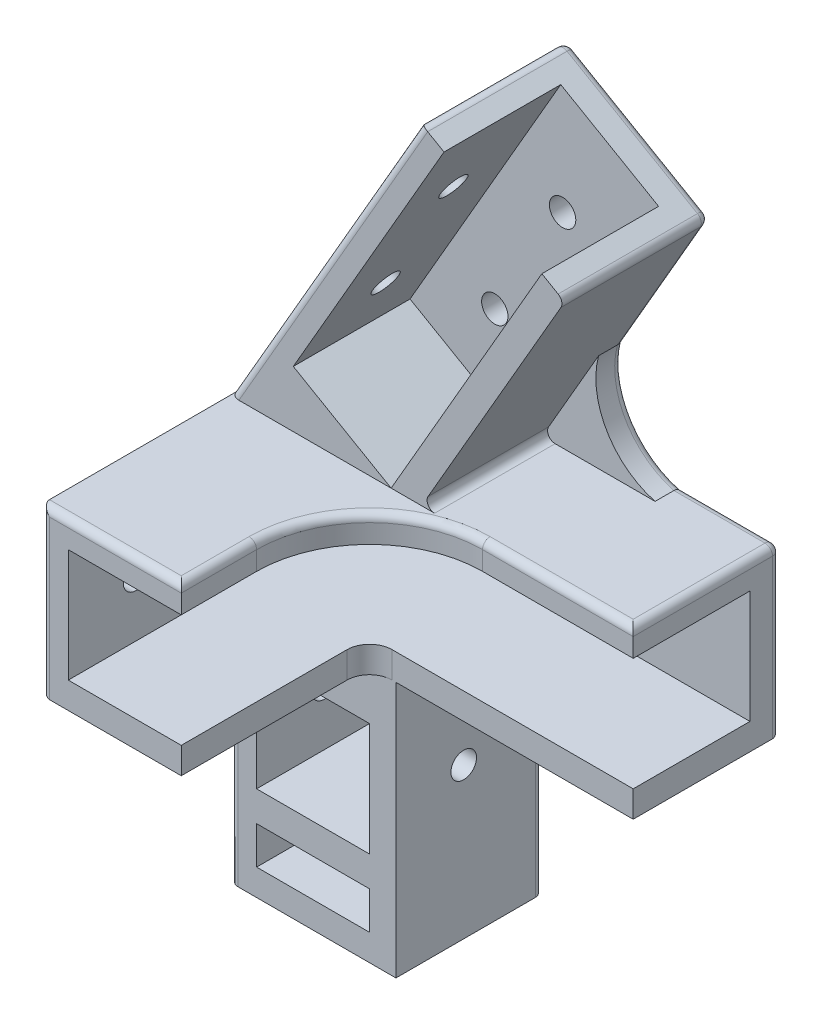
SolidWorks part; units mm, degrees
ref_plane "Front Plane" through (0, 0, 0) normal (0, 0, 1) x (1, 0, 0)
ref_plane "Top Plane" through (0, 0, 0) normal (0, 1, 0) x (1, 0, 0)
ref_plane "Right Plane" through (0, 0, 0) normal (1, 0, 0) x (0, 0, -1)
sketch "Sketch1" plane through (0, 0, 0) normal (0, 0, 1) x (1, 0, 0)
  line L1 (-5.6994, 32.9163) -> (16.3006, 32.9163)
  line L2 (-5.6994, 10.9163) -> (-5.6994, -23.0837)
  line L3 (-5.6994, -23.0837) -> (16.3006, -23.0837)
  line L4 (16.3006, 32.9163) -> (16.3006, -23.0837)
  line L5 (-5.6994, 10.9163) -> (-37.1994, 10.9163)
  line L7 (-5.6994, 32.9163) -> (-37.1994, 32.9163)
  line L8 (-37.1994, 10.9163) -> (-37.1994, 32.9163)
  dimension "D1" = 22
  dimension "D2" = 22
  dimension "D3" = 56
  dimension "D4" = 53.5
extrude "Boss-Extrude1" add sketch "Sketch1" along normal blind 19.5
sketch "Sketch3" plane through (0, 0, 19.5) normal (0, 0, 1) x (1, 0, 0)
  line L1 (16.3006, 32.9163) -> (-2.1994, 32.9163)
  line L2 (16.3006, 32.9163) -> (16.3006, 10.9163)
  line L3 (16.3006, 10.9163) -> (-2.1994, 10.9163)
  line L4 (-2.1994, 32.9163) -> (-2.1994, 10.9163)
  dimension "D1" = 18.5
extrude "Boss-Extrude2" add sketch "Sketch3" along normal blind 25
sketch "Sketch5" plane through (0, 0, 44.5) normal (0, 0, 1) x (1, 0, 0)
  line L0 (-37.1994, 32.9163) -> (-37.1994, 10.9163) construction
  line L1 (-37.1994, 29.4163) -> (12.8006, 29.4163)
  line L2 (-37.1994, 29.4163) -> (-37.1994, 14.4163)
  line L3 (-37.1994, 14.4163) -> (12.8006, 14.4163)
  line L4 (12.8006, 29.4163) -> (12.8006, 14.4163)
  line L5 (16.3006, 10.9163) -> (16.3006, 32.9163) construction
  line L6 (-2.1994, 4.4163) -> (12.8006, 4.4163)
  line L7 (-2.1994, 4.4163) -> (-2.1994, -10.5837)
  line L8 (-2.1994, -10.5837) -> (12.8006, -10.5837)
  line L9 (12.8006, 4.4163) -> (12.8006, -10.5837)
  line L12 (-2.1994, 32.9163) -> (-37.1994, 32.9163) construction
  line L13 (-2.1994, 10.9163) -> (16.3006, 10.9163) construction
  line L15 (16.3006, -23.0837) -> (16.3006, 10.9163) construction
  line L16 (-5.6994, -23.0837) -> (16.3006, -23.0837) construction
  line L17 (-2.1994, -14.5837) -> (12.8006, -14.5837)
  line L18 (-2.1994, -14.5837) -> (-2.1994, -19.5837)
  line L19 (-2.1994, -19.5837) -> (12.8006, -19.5837)
  line L20 (12.8006, -14.5837) -> (12.8006, -19.5837)
  dimension "D1" = 3.5
  dimension "D2" = 6.5
  dimension "D3" = 15
  dimension "D4" = 3.5
  dimension "D5" = 15
  dimension "D6" = 15
  dimension "D7" = 3.5
  dimension "D8" = 15
  dimension "D9" = 4
  dimension "D10" = 3.5
extrude "Cut-Extrude1" cut sketch "Sketch5" against normal offset from surface (40.5 mm away) 4 up to face at (-8.8661, 6.9163, 0)
sketch "Sketch7" plane through (16.3006, 0, 0) normal (1, 0, 0) x (0, 0, -1)
  line L0 (-34.5, 10.9163) -> (-19.5, 10.9163)
  line L1 (-44.5, 10.9163) -> (-19.5, 10.9163) construction
  line L2 (-19.5, 10.9163) -> (-19.5, -4.0837)
  line L3 (-19.5, -23.0837) -> (-19.5, 10.9163) construction
  arc A0 (-34.5, 10.9163) -> (-19.5, -4.0837) centre (-34.5, -4.0837) cw
  dimension "D1" = 15
extrude "Boss-Extrude4" add sketch "Sketch7" against normal blind 3.5
sketch "Sketch8" plane through (0, 0, 0) normal (0, 0, -1) x (-1, 0, 0)
  line L0 (5.6994, 10.9163) -> (20.6994, 10.9163)
  line L1 (37.1994, 10.9163) -> (5.6994, 10.9163) construction
  line L2 (5.6994, 10.9163) -> (5.6994, -4.0837)
  line L3 (5.6994, 10.9163) -> (5.6994, -23.0837) construction
  arc A0 (20.6994, 10.9163) -> (5.6994, -4.0837) centre (20.6994, -4.0837) ccw
  dimension "D1" = 15
extrude "Boss-Extrude5" add sketch "Sketch8" against normal blind 3.5
sketch "Sketch9" plane through (0, 32.9163, 0) normal (0, 1, 0) x (1, 0, 0)
  line L0 (-2.1994, -34.5) -> (-2.1994, -19.5)
  line L1 (-2.1994, -44.5) -> (-2.1994, -19.5) construction
  line L2 (-2.1994, -19.5) -> (-17.1994, -19.5)
  line L3 (-2.1994, -19.5) -> (-37.1994, -19.5) construction
  arc A0 (-2.1994, -34.5) -> (-17.1994, -19.5) centre (-17.1994, -34.5) ccw
  dimension "D1" = 15
extrude "Boss-Extrude6" add sketch "Sketch9" against normal blind 3.5
fillet "Fillet3" radius 3 1 edges
sketch "Sketch11" plane through (0, 0, 0) normal (0, 0, -1) x (-1, 0, 0)
  line L0 (1.1994, -23.0837) -> (1.1994, 10.9163) construction
  line L2 (5.6994, -23.0837) -> (-16.3006, -23.0837) construction
  line L5 (5.6994, -4.0837) -> (5.6994, -23.0837) construction
  text T0 "MR.3" font "Century Gothic" height 12
  dimension "D1" = 4.5
extrude "Cut-Extrude3" cut sketch "Sketch11" against normal blind 1
sketch "Sketch12" plane through (0, 0, 0) normal (0, 0, -1) x (-1, 0, 0)
  line L0 (37.1994, 21.9163) -> (-16.3006, 21.9163) construction
  line L1 (37.1994, 32.9163) -> (37.1994, 10.9163) construction
  line L2 (-16.3006, -23.0837) -> (-16.3006, 32.9163) construction
  line L3 (-12.8006, 14.4163) -> (-12.8006, 29.4163) construction
  circle A0 centre (-5.3006, 21.9163) radius 1.7
  circle A1 centre (10.9494, 21.9163) radius 1.7
  circle A2 centre (27.1994, 21.9163) radius 1.7
  dimension "D4" = 3.4
  dimension "D1" = 7.5
  dimension "D2" = 10
  dimension "D3" = 16.25
extrude "Cut-Extrude4" cut sketch "Sketch12" against normal blind 5
sketch "Sketch13" plane through (-5.6994, 0, 0) normal (-1, 0, 0) x (0, 0, 1)
  line L0 (4, 4.4163) -> (19.5, 4.4163) construction
  line L1 (19.5, 10.9163) -> (19.5, -23.0837) construction
  circle A0 centre (10.5, -3.0837) radius 1.7
  dimension "D2" = 9
  dimension "D3" = 3.4
  dimension "D1" = 7.5
extrude "Cut-Extrude5" cut sketch "Sketch13" against normal blind 45
sketch "Sketch14" plane through (16.3006, 0, 0) normal (1, 0, 0) x (0, 0, -1)
  line L0 (-10.5, -3.0837) -> (-10.5, 32.9163) construction
  line L1 (-44.5, 32.9163) -> (0, 32.9163) construction
  line L2 (-44.5, 21.9163) -> (-10.5, 21.9163) construction
  line L3 (-44.5, 10.9163) -> (-44.5, 32.9163) construction
  circle A0 centre (-10.5, 21.9163) radius 1.7
  circle A1 centre (-35.5, 21.9163) radius 1.7
  dimension "D1" = 3.4
  dimension "D2" = 9
extrude "Cut-Extrude6" cut sketch "Sketch14" against normal blind 45
sketch "Sketch15" plane through (0, -23.0837, 0) normal (0, -1, 0) x (1, 0, 0)
  line L0 (16.3006, 9.75) -> (-5.6994, 9.75) construction
  line L1 (16.3006, 19.5) -> (16.3006, 0) construction
  line L2 (-5.6994, 19.5) -> (-5.6994, 0) construction
  line L3 (5.3006, 19.5) -> (5.3006, 0) construction
  line L4 (-5.6994, 19.5) -> (16.3006, 19.5) construction
  line L5 (-5.6994, 0) -> (16.3006, 0) construction
  circle A0 centre (5.3006, 9.75) radius 1.7
  dimension "D1" = 3.4
extrude "Cut-Extrude7" cut sketch "Sketch15" against normal blind 4
mirror "Mirror2" about plane through (16.3006, 32.9163, 19.5) normal (-1, 0, 0) of "Cut-Extrude7", "Cut-Extrude6", "Cut-Extrude5", "Cut-Extrude4", "Fillet3", "Boss-Extrude6", "Boss-Extrude5", "Boss-Extrude4", "Cut-Extrude1", "Boss-Extrude2", "Boss-Extrude1"
sketch "Sketch16" plane through (0, 0, 0) normal (0, 0, -1) x (-1, 0, 0)
  line L0 (-69.8006, 32.9163) -> (37.1994, 32.9163) construction
  line L1 (-16.3006, 32.9163) -> (53.9943, 32.9163)
  line L2 (-16.3006, 32.9163) -> (-16.3006, -24.95)
  line L3 (-16.3006, -24.95) -> (53.9943, -24.95)
  line L4 (53.9943, 32.9163) -> (53.9943, -24.95)
extrude "Cut-Extrude8" cut sketch "Sketch16" against normal blind 72
sketch "Sketch20" plane through (0, 0, 0) normal (0, 0, -1) x (-1, 0, 0)
  line L0 (-22.3006, -23.0837) -> (-22.3006, 16.9163) construction
  line L1 (-16.3006, -23.0837) -> (-38.3006, -23.0837) construction
  line L2 (-16.3006, 32.9163) -> (-16.3006, -23.0837) construction
  text T0 "ALFR3D" font "Murder Of Mayday" height 10
  dimension "D1" = 6
  dimension "D2" = 40
extrude "Cut-Extrude9" [suppressed] cut sketch "Sketch20" against normal blind 1
sketch "Sketch21" plane through (0, 0, 0) normal (0, 0, -1) x (-1, 0, 0)
  line L0 (-16.3006, 32.9163) -> (-41.6514, 76.8252)
  line L1 (-41.6514, 76.8252) -> (-60.704, 65.8252)
  line L2 (-60.704, 65.8252) -> (-41.704, 32.9163)
  line L3 (-69.8006, 32.9163) -> (-16.3006, 32.9163) construction
  line L4 (-41.704, 32.9163) -> (-16.3006, 32.9163)
  dimension "D1" = 22
  dimension "D2" = 60
  dimension "D3" = 38
extrude "Boss-Extrude7" add sketch "Sketch21" against normal up to surface (19.5 mm away) up to face at (57.3006, 31.1663, 19.5)
sketch "Sketch22" plane through (0, 0, 19.5) normal (0, 0, 1) x (1, 0, 0)
  line L0 (44.6825, 75.0752) -> (24.6722, 40.4163)
  line L1 (60.704, 65.8252) -> (41.6514, 76.8252) construction
  line L2 (24.6722, 40.4163) -> (37.6625, 32.9163)
  line L3 (37.6625, 32.9163) -> (57.6729, 67.5752)
  line L4 (57.6729, 67.5752) -> (44.6825, 75.0752)
  line L5 (41.6514, 76.8252) -> (16.3006, 32.9163) construction
  line L7 (16.3006, 32.9163) -> (41.704, 32.9163) construction
  dimension "D1" = 15
  dimension "D2" = 3.5
extrude "Cut-Extrude10" cut sketch "Sketch22" against normal up to surface (15.5 mm away) up to face at (41.8506, 21.9163, 4)
sketch "Sketch23" plane through (0, 0, 0) normal (0, 0, -1) x (-1, 0, 0)
  line L0 (-56.704, 32.9163) -> (-41.704, 32.9163)
  line L1 (-69.8006, 32.9163) -> (-41.704, 32.9163) construction
  line L2 (-41.704, 32.9163) -> (-49.204, 45.9066)
  line L3 (-60.704, 65.8252) -> (-41.704, 32.9163) construction
  arc A0 (-56.704, 32.9163) -> (-49.204, 45.9066) centre (-59.4497, 43.1617) ccw
  dimension "D2" = 10.607
  dimension "D1" = 15
extrude "Boss-Extrude8" add sketch "Sketch23" against normal blind 3.5
fillet "Fillet4" radius 1 22 edges at (16.3006, 10.9163, 39.5) (16.3006, 6.5229, 23.8934) (61.5506, 10.9163, 0) (42.694, 6.5229, 0) (34.8006, 32.9163, 39.5) (50.2637, 37.8582, 0) (28.976, 54.8707, 0) (16.3006, -13.5837, 19.5) (16.3006, 4.9163, 0) (38.3006, -13.5837, 0) (69.8006, 32.9163, 9.75) (69.8006, 21.9163, 0) (16.3006, 21.9163, 44.5) (39.194, 32.9163, 23.8934) (25.5506, 32.9163, 44.5) (41.6514, 76.8252, 9.75) (51.1777, 71.3252, 0) (60.704, 65.8252, 9.75)
fillet "Fillet5" radius 1 1 edges
sketch "Sketch24" plane through (-2.0277, 1.1707, 0) normal (-0.866, 0.5, 0) x (0, 0, 1)
  line L0 (12, 36.6566) -> (12, 88.887) construction
  line L1 (18.5, 36.6566) -> (1, 36.6566) construction
  line L2 (19.5, 87.3583) -> (19.5, 37.234) construction
  line L3 (1, 87.3583) -> (19.5, 87.3583) construction
  line L4 (19.5, 44.354) -> (1, 44.354) construction
  circle A0 centre (12, 74.8583) radius 1.75
  circle A1 centre (12, 56.854) radius 1.75
  dimension "D2" = 3.5
  dimension "D3" = 12.5
  dimension "D4" = 12.5
  dimension "D1" = 7.5
extrude "Cut-Extrude11" cut sketch "Sketch24" against normal blind 10
sketch "Sketch25" plane through (0, 0, 0) normal (0, 0, -1) x (-1, 0, 0)
  line L0 (-51.1777, 71.3252) -> (-31.1674, 36.6663) construction
  line L1 (-59.838, 66.3252) -> (-42.5175, 76.3252) construction
  line L2 (-24.6722, 40.4163) -> (-37.6625, 32.9163) construction
  line L3 (-27.2743, 51.9233) -> (-30.3054, 50.1733) construction
  circle A0 centre (-44.9277, 60.4999) radius 1.75
  circle A1 centre (-35.9256, 44.9078) radius 1.75
  dimension "D1" = 3.5
  dimension "D2" = 12.5
  dimension "D3" = 1.75
extrude "Cut-Extrude12" cut sketch "Sketch25" against normal blind 10
